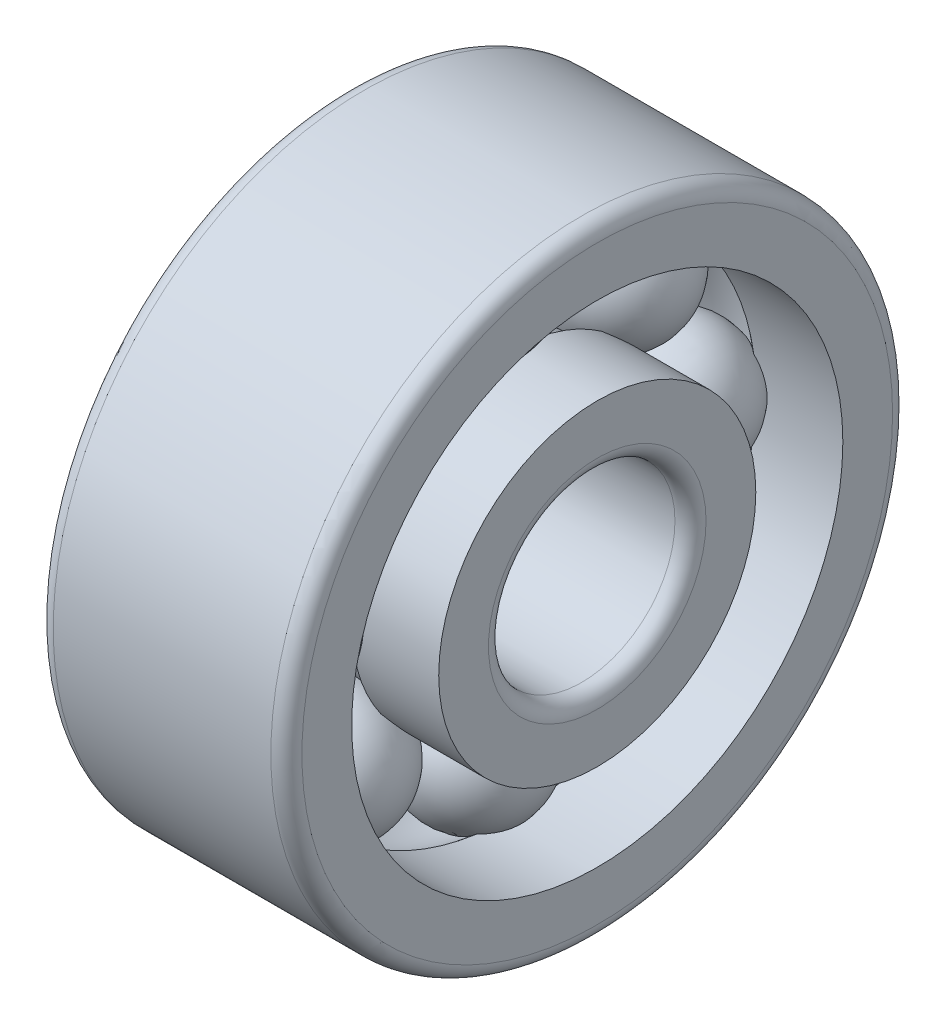
SolidWorks part; units mm, degrees
ref_plane "Plane1" through (0, 0, 0) normal (0, 0, 1) x (1, 0, 0)
ref_plane "Plane2" through (0, 0, 0) normal (0, 1, 0) x (1, 0, 0)
ref_plane "Plane3" through (0, 0, 0) normal (1, 0, 0) x (0, 0, -1)
sketch "Clipboard" plane through (0, 0, 0) normal (0, 0, 1) x (1, 0, 0)
  line L0 (-10, 0) -> (10, 0) construction
  line L1 (0, 0) -> (22.1431, -3.112)
  line L2 (0, 0) -> (0.6437, 0.0905)
  line L3 (0, 0) -> (22.1431, -3.112)
  line L4 (0, 0) -> (-22.3573, -0.3902)
  dimension "BallCLRad" = 0.65
sketch "CagSpiSke" plane through (0, 0, 0) normal (0, 0, 1) x (1, 0, 0)
  line L0 (0.021, 0.615) -> (0.021, 0.685)
  line L1 (0.021, 0.685) -> (-0.021, 0.685)
  line L2 (-0.021, 0.685) -> (-0.021, 0.615)
  line L3 (-0.021, 0.615) -> (0.021, 0.615)
  line L4 (-20.6375, 0) -> (20.6375, 0) construction
  line L5 (0, 0) -> (0, 23.7692) construction
  dimension "OD" = 1.37
  dimension "ID" = 1.23
revolve "CageSpine" add sketch "CagSpiSke" angle 0.001 about L4 reverse direction yes
ref_axis "Axis1" through (-50, 0, 0) along (1, 0, 0)
sketch "CagBalSke" plane through (0, 0, 0) normal (0, 0, 1) x (1, 0, 0)
  line L0 (-0.231, 0.65) -> (0.231, 0.65)
  line L1 (-1.905, 0.65) -> (1.905, 0.65) construction
  line L2 (-10, 0) -> (10, 0) construction
  line L3 (0, 0) -> (0, 24) construction
  arc A0 (0.231, 0.65) -> (-0.231, 0.65) centre (0, 0.65) cw
  dimension "BallCLRad" = 0.65
revolve "CageBall" [suppressed] add sketch "CagBalSke" angle 360 about L1 reverse direction yes
pattern_circular "CageBalls" [suppressed] count 8 every 45 about axis through (-50, 0, 0) along (1, 0, 0)
sketch "CagTrmODSke" plane through (0, 0, 0) normal (0, 0, 1) x (1, 0, 0)
  line L0 (0.232, 0.685) -> (0.232, 0.882)
  line L1 (0.232, 0.882) -> (-0.232, 0.882)
  line L2 (-0.232, 0.882) -> (-0.232, 0.685)
  line L3 (-0.232, 0.685) -> (0.232, 0.685)
  line L4 (-20.6375, 0) -> (20.6375, 0) construction
  line L5 (0, 0) -> (0, 25) construction
  dimension "Width" = 0.464
  dimension "ID" = 1.37
  dimension "OD" = 1.764
revolve "CageTrimOD" [suppressed] cut sketch "CagTrmODSke" angle 360 about L4 reverse direction yes
sketch "CagTrmIDSke" plane through (0, 0, 0) normal (0, 0, 1) x (1, 0, 0)
  line L0 (0.232, 0.42) -> (0.232, 0.615)
  line L1 (0.232, 0.615) -> (-0.232, 0.615)
  line L2 (-0.232, 0.615) -> (-0.232, 0.42)
  line L3 (-0.232, 0.42) -> (0.232, 0.42)
  line L4 (-20.6375, 0) -> (20.6375, 0) construction
  line L5 (0, 0) -> (0, 25) construction
  dimension "Width" = 0.464
  dimension "ID" = 0.84
  dimension "OD" = 1.23
revolve "CageTrimID" [suppressed] cut sketch "CagTrmIDSke" angle 360 about L4 reverse direction yes
sketch "BalSimSke" plane through (0, 0, 0) normal (0, 0, 1) x (1, 0, 0)
  line L0 (-10, 0) -> (10, 0) construction
  line L1 (-10, 0.65) -> (10, 0.65) construction
  line L2 (0, 0) -> (0, 23) construction
  circle A0 centre (0, 0.65) radius 0.21
  dimension "BallCLRad" = 0.65
  dimension "Ball_diameter" = 0.42
revolve "BallsSimplified" [suppressed] add sketch "BalSimSke" angle 360 about L0
sketch "BalDetSke" plane through (0, 0, 0) normal (0, 0, 1) x (1, 0, 0)
  line L0 (-0.21, 0.65) -> (0.21, 0.65)
  line L1 (-1.905, 0.65) -> (1.905, 0.65) construction
  line L2 (0, 0) -> (0, 25) construction
  arc A0 (0.21, 0.65) -> (-0.21, 0.65) centre (0, 0.65) cw
  dimension "BallCLRad" = 0.65
  dimension "Ball_diameter" = 0.42
revolve "BallDetailed" add sketch "BalDetSke" angle 360 about L1 reverse direction yes
sketch "InnRacSke" plane through (0, 0, 0) normal (0, 0, 1) x (1, 0, 0)
  line L0 (-0.1209, 0.51) -> (-0.4, 0.51)
  line L1 (-0.4, 0.51) -> (-0.4, 0.35)
  line L2 (-0.35, 0.3) -> (0.35, 0.3)
  line L3 (0.4, 0.35) -> (0.4, 0.51)
  line L4 (0.4, 0.51) -> (0.1209, 0.51)
  line L5 (-20.6375, 0) -> (20.6375, 0) construction
  line L6 (0, 0) -> (0, 30) construction
  arc A0 (-0.4, 0.35) -> (-0.35, 0.3) centre (-0.35, 0.35) ccw
  arc A1 (0.35, 0.3) -> (0.4, 0.35) centre (0.35, 0.35) ccw
  arc A2 (0.1209, 0.51) -> (-0.1209, 0.51) centre (0, 0.65) cw
  dimension "BallCLRad" = 0.65
  dimension "Fillet_radius" = 0.05
  dimension "Ball_diameter" = 0.37
  dimension "ID" = 0.6
  dimension "OD" = 1.02
  dimension "Width" = 0.8
revolve "InnerRace" add sketch "InnRacSke" angle 360 about L5 reverse direction yes
sketch "OutRacSke" plane through (0, 0, 0) normal (0, 0, 1) x (1, 0, 0)
  line L0 (-0.1209, 0.79) -> (-0.4, 0.79)
  line L1 (-0.4, 0.79) -> (-0.4, 0.95)
  line L2 (-0.35, 1) -> (0.35, 1)
  line L3 (0.4, 0.95) -> (0.4, 0.79)
  line L4 (0.4, 0.79) -> (0.1209, 0.79)
  line L5 (-20.6375, 0) -> (20.6375, 0) construction
  line L6 (0, 0) -> (0, 30) construction
  arc A0 (-0.4, 0.95) -> (-0.35, 1) centre (-0.35, 0.95) cw
  arc A1 (0.35, 1) -> (0.4, 0.95) centre (0.35, 0.95) cw
  arc A2 (0.1209, 0.79) -> (-0.1209, 0.79) centre (0, 0.65) ccw
  dimension "BallCLRad" = 0.65
  dimension "Fillet_radius" = 0.05
  dimension "Ball_diameter" = 0.37
  dimension "Width" = 0.8
revolve "OuterRace" add sketch "OutRacSke" angle 360 about L5 reverse direction yes
pattern_circular "BallsDetailed" count 8 every 45 about axis through (-50, 0, 0) along (1, 0, 0) of "BallDetailed"
equation "\"BallCLRad@Clipboard\" = ( \"OD@OutRacSke\" + \"ID@InnRacSke\" ) / 4"
equation "\"BallCLRad@BalSimSke\" = \"BallCLRad@Clipboard\""
equation "\"BallCLRad@BalDetSke\" = \"BallCLRad@Clipboard\""
equation "\"BallCLRad@InnRacSke\" = \"BallCLRad@Clipboard\""
equation "\"BallCLRad@OutRacSke\" = \"BallCLRad@Clipboard\""
equation "\"Ball_diameter@InnRacSke\" = \"Ball_diameter@BalDetSke\" - 0.05"
equation "\"Ball_diameter@OutRacSke\" = \"Ball_diameter@BalDetSke\" - 0.05"
equation "\"Ball_diameter@BalSimSke\" = \"Ball_diameter@BalDetSke\""
equation "\"Width@OutRacSke\" = \"Width@InnRacSke\""
equation "\"Fillet_radius@OutRacSke\" = \"Fillet_radius@InnRacSke\""
equation "\"Max_count@Clipboard\" = int( 3.14159265 / atn(( \"Ball_diameter@BalDetSke\" / 2) / sqr( \"BallCLRad@Clipboard\"  *  \"BallCLRad@Clipboard\" - ( \"Ball_diameter@BalDetSke\" / 2) *  ( \"Ball_diameter@BalDetSke\" / 2))))"
equation "\"Max_count@Clipboard\" = ((sgn( \"Max_count@Clipboard\" - \"Count@Clipboard\" )-1)*( \"Max_count@Clipboard\" - \"Count@Clipboard\" ))/-2+ \"Count@Clipboard\""
equation "\"Count@BallsDetailed\" = int( \"Show_count@Clipboard\" ) "
equation "\"Count@BallsDetailed\" = ((sgn( \"Count@BallsDetailed\" - \"Max_count@Clipboard\" )-1)*( \"Count@BallsDetailed\" - \"Max_count@Clipboard\" ))/-2+ \"Max_count@Clipboard\""
equation "\"Count@BallsDetailed\" = ((sgn( \"Count@BallsDetailed\" - \"Min_count@Clipboard\" )+1)*( \"Count@BallsDetailed\" - \"Min_count@Clipboard\"))/2 +\"Min_count@Clipboard\""
equation "\"Angle@BallsDetailed\" = 360.0 / \"Max_count@Clipboard\""
equation "\"BallCLRad@CagBalSke\" = \"BallCLRad@Clipboard\""
equation "\"Count@CageBalls\" = \"Count@BallsDetailed\""
equation "\"Angle@CageBalls\" = \"Angle@BallsDetailed\""
equation "\"Angle@CageSpine\" =  \"Angle@CageBalls\" * ( \"Count@CageBalls\" -1 + int( \"Count@CageBalls\" / \"Max_count@Clipboard\" ) )  + 0.001 -  int( \"Count@CageBalls\" / \"Max_count@Clipboard\" ) * 0.001"
equation "\"Angle@CageSpine\" =  \"Angle@CageSpine\" * int( \"Min_count@Clipboard\" / 2) + int(1 / \"Min_count@Clipboard\")  * 0.001"
equation "\"CageWallOD@CagBalSke\" =  \"Ball_diameter@BalDetSke\" * 1.1"
equation "\"Thickness@CagSpiSke\" =  \"Ball_diameter@BalDetSke\" * 0.1"
equation "\"OD@CagTrmODSke\" = \"BallCLRad@Clipboard\" * 2 + \"CageWallOD@CagBalSke\" + 0.002"
equation "\"ID@CagTrmODSke\" = \"BallCLRad@Clipboard\" * 2 + \"Ball_diameter@BalDetSke\" / 6"
equation "\"OD@CagTrmIDSke\" = \"BallCLRad@Clipboard\" * 2 - \"Ball_diameter@BalDetSke\" / 6"
equation "\"ID@CagTrmIDSke\" = \"BallCLRad@Clipboard\" * 2 - \"CageWallOD@CagBalSke\" + 0.002"
equation "\"OD@CagSpiSke\" = \"ID@CagTrmODSke\""
equation "\"ID@CagSpiSke\" = \"OD@CagTrmIDSke\""
equation "\"Width@CagTrmODSke\" = \"CageWallOD@CagBalSke\" + 0.002"
equation "\"Width@CagTrmIDSke\" = \"CageWallOD@CagBalSke\" + 0.002"
